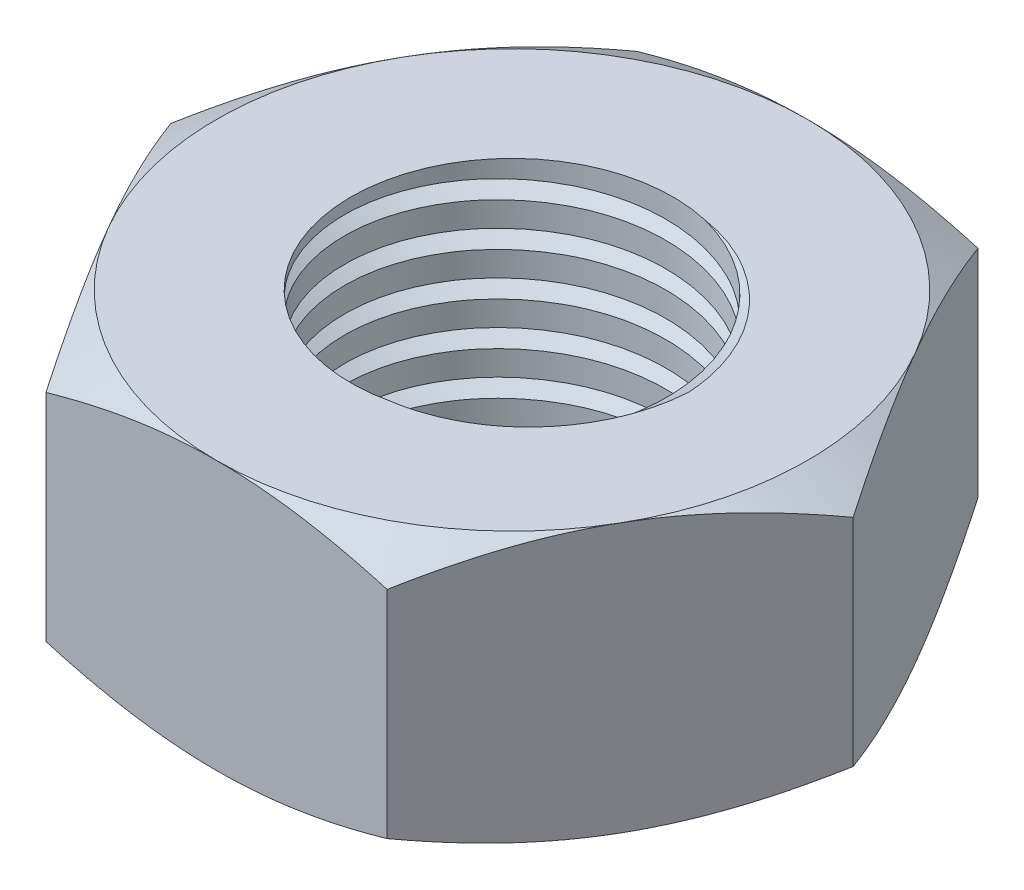
SolidWorks part; units mm, degrees
ref_plane "Front Plane" through (0, 0, 0) normal (0, 0, 1) x (1, 0, 0)
ref_plane "Top Plane" through (0, 0, 0) normal (0, 1, 0) x (1, 0, 0)
ref_plane "Right Plane" through (0, 0, 0) normal (1, 0, 0) x (0, 0, -1)
sketch "Sketch1" plane through (0, 0, 0) normal (0, 1, 0) x (1, 0, 0)
  line L0 (3.1754, 0) -> (1.5877, 2.75)
  line L1 (-3.1754, 0) -> (-1.5877, -2.75)
  line L2 (-1.5877, -2.75) -> (1.5877, -2.75)
  line L3 (1.5877, -2.75) -> (3.1754, 0)
  line L4 (1.5877, 2.75) -> (-1.5877, 2.75)
  line L5 (-1.5877, 2.75) -> (-3.1754, 0)
  circle A0 centre (0, 0) radius 2.75 construction
  dimension "D1" = 5.5
extrude "Boss-Extrude1" add sketch "Sketch1" along normal blind 2.5
sketch "Sketch2" plane through (0, 2.5, 0) normal (0, 1, 0) x (1, 0, 0)
  circle A0 centre (0, 0) radius 1.5
  dimension "D1" = 3
extrude "Cut-Extrude1" cut sketch "Sketch2" against normal blind 2.5
sketch "Sketch3" plane through (0, 2.5, 0) normal (0, 1, 0) x (1, 0, 0)
  circle A0 centre (0, 0) radius 2.75
  dimension "D1" = 5.5
extrude "Cut-Extrude3" cut sketch "Sketch3" against normal blind 0.5 draft 60 flip side to cut
sketch "Sketch4" plane through (0, 0, 0) normal (0, -1, 0) x (1, 0, 0)
  circle A0 centre (0, 0) radius 2.75
  dimension "D1" = 5.5
extrude "Cut-Extrude4" cut sketch "Sketch4" against normal blind 0.5 draft 60 flip side to cut
sketch "Sketch9" plane through (0, 2.5, 0) normal (0, 1, 0) x (1, 0, 0)
  circle A0 centre (0, 0) radius 1.5
  dimension "D1" = 3
curve "Helix/Spiral1" pitch 0.4 height 4 turns 10
sketch3d "3DSketch1"
  line L0 (1.3528, -1.67, 0) -> (1.3528, -1.33, 0)
  line L1 (1.3528, -1.33, 0) -> (1.6472, -1.5, 0)
  line L2 (1.6472, -1.5, 0) -> (1.3528, -1.67, 0)
  dimension "D1" = 0.34
  dimension "D2" = 0.34
  dimension "D3" = 0.34
sweep "Cut-Sweep1" cut profiles "3DSketch1" path "Helix/Spiral1"
